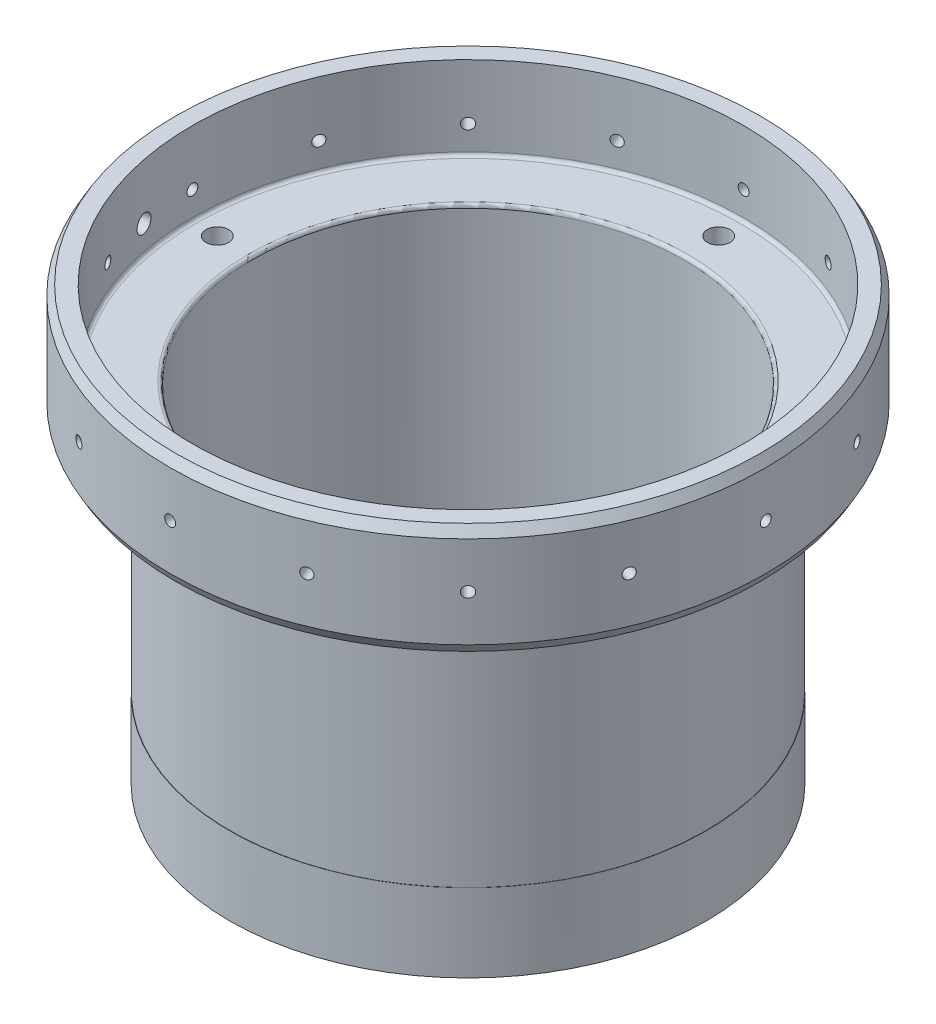
SolidWorks part; units mm, degrees
material "6061-T6 (SS)"
ref_plane "Front Plane" through (0, 0, 0) normal (0, 0, 1) x (1, 0, 0)
ref_plane "Top Plane" through (0, 0, 0) normal (0, 1, 0) x (1, 0, 0)
ref_plane "Right Plane" through (0, 0, 0) normal (1, 0, 0) x (0, 0, -1)
sketch "Sketch1" plane through (0, 0, 0) normal (0, 0, 1) x (1, 0, 0)
  line L0 (0, 0) -> (0, 9.1321) construction
  line L1 (0, 0) -> (-63.119, 0) construction
  line L2 (-63.119, 0) -> (-68.199, 0)
  line L3 (-68.199, 0) -> (-68.199, -25.4)
  line L4 (-68.199, -25.4) -> (-54.6024, -25.4)
  line L5 (-54.6024, -25.4) -> (-54.6024, -33.909)
  line L6 (-54.5516, -99.6696) -> (-49.4665, -99.6696)
  line L7 (-49.4665, -99.6696) -> (-49.4665, -19.05)
  line L8 (-49.4665, -19.05) -> (-63.119, -19.05)
  line L9 (-63.119, -19.05) -> (-63.119, 0)
  line L10 (-54.6024, -33.909) -> (-54.4881, -33.909)
  line L11 (-54.4881, -33.909) -> (-54.4881, -81.026)
  line L12 (-54.4881, -81.026) -> (-54.5516, -81.026)
  line L13 (-54.5516, -81.026) -> (-54.5516, -99.6696)
  dimension "D1" = 5.08
  dimension "D2" = 68.199
  dimension "D3" = 25.4
  dimension "D4" = 6.35
  dimension "D5" = 74.2696
  dimension "D6" = 49.4665
  dimension "D7" = 54.5516
  dimension "D8" = 8.509
  dimension "D9" = 47.117
  dimension "D10" = 54.6024
  dimension "D11" = 54.4881
revolve "Revolve6" add sketch "Sketch1" angle 360 about L0
sketch "Sketch2" plane through (0, 0, 0) normal (0, 1, 0) x (1, 0, 0)
  line L0 (0, 0) -> (-68.199, 0) construction
  line L1 (0, 0) -> (-66.8886, -13.305) construction
  circle A0 centre (0, 0) radius 68.199 construction
  dimension "D1" = 11.25
ref_plane "Plane1" through (-68.199, 0, 0) normal (-1, 0, 0) x (0, 0, 1)
sketch "Sketch3" plane through (-68.199, 0, 0) normal (-1, 0, 0) x (0, 0, 1)
  line L0 (0, 0) -> (0, -12.7) construction
  dimension "D1" = 12.7
hole_wizard "Tap Drill for M3x0.5 Tap1" positions "Sketch5" profile "Sketch4" hole size "M3x0.5" standard "Ansi Metric"
sketch "Sketch5" plane through (-68.199, 0, 0) normal (-1, 0, 0) x (0, 0, 1)
  point P1 (0, -12.7)
sketch "Sketch4" plane through (-68.199, -12.7, 0) normal (0, 1, 0) x (0, 0, 1)
  line L0 (0, 0) -> (0, 10.9111)
  line L1 (0, 10.9111) -> (1.25, 10.16)
  line L2 (1.25, 10.16) -> (1.25, 0)
  line L5 (1.25, 0) -> (0, 0)
  line L10 (0, 10.9111) -> (-1.25, 10.16) construction
  line L11 (0, -6.35) -> (0, 107.95) construction
  dimension "Hole Dia." = 2.5
  dimension "Hole Depth" = 10.16
  dimension "Drill Angle" = 118
pattern_circular "CirPattern1" count 16 over 360 about axis through (0, 0, 0) along (0, -1, 0) of "Tap Drill for M3x0.5 Tap1"
ref_plane "Plane2" through (-66.8886, 0, 13.305) normal (-0.9808, 0, 0.1951) x (0.1951, 0, 0.9808)
sketch "Sketch6" plane through (-66.8886, 0, 13.305) normal (-0.9808, 0, 0.1951) x (0.1951, 0, 0.9808)
  line L0 (0, 0) -> (0, -12.7) construction
  dimension "D1" = 12.7
hole_wizard "Tap Drill for #10-32 Tap1" positions "Sketch8" profile "Sketch7" hole size "#10-32" standard "Ansi Inch"
sketch "Sketch8" plane through (-66.8886, 0, 13.305) normal (-0.9808, 0, 0.1951) x (0.1951, 0, 0.9808)
  point P1 (0, -12.7)
sketch "Sketch7" plane through (-66.8886, -12.7, 13.305) normal (0, 1, 0) x (0.1951, 0, 0.9808)
  line L0 (0, 0) -> (0, 11.3733)
  line L1 (0, 11.3733) -> (2.0193, 10.16)
  line L2 (2.0193, 10.16) -> (2.0193, 0)
  line L5 (2.0193, 0) -> (0, 0)
  line L10 (0, 11.3733) -> (-2.0193, 10.16) construction
  line L11 (0, -6.35) -> (0, 107.95) construction
  dimension "Hole Dia." = 4.0386
  dimension "Hole Depth" = 10.16
  dimension "Drill Angle" = 118
sketch "Sketch9" plane through (0, -99.6696, 0) normal (0, -1, 0) x (1, 0, 0)
  line L0 (54.5516, 0) -> (49.4665, 0) construction
  circle A2 centre (0, 0) radius 49.4665 construction
  circle A3 centre (0, 0) radius 54.5516 construction
  point P9 (52.009, 0)
  dimension "D1" = 52.009
hole_wizard "Tap Drill for #4-40 Tap1" positions "3DSketch1" profile "Sketch10" hole size "#4-40" standard "Ansi Inch"
sketch3d "3DSketch1"
  point P0 (52.009, -99.6696, 0)
sketch "Sketch10" plane through (52.009, -99.6696, 0) normal (1, 0, 0) x (0, 0, -1)
  line L0 (0, 0) -> (0, 18.4592)
  line L1 (0, 18.4592) -> (1.1303, 17.78)
  line L2 (1.1303, 17.78) -> (1.1303, 0)
  line L5 (1.1303, 0) -> (0, 0)
  line L10 (0, 18.4592) -> (-1.1303, 17.78) construction
  line L11 (0, -6.35) -> (0, 107.95) construction
  dimension "Hole Dia." = 2.2606
  dimension "Hole Depth" = 17.78
  dimension "Drill Angle" = 118
pattern_circular "CirPattern2" count 16 over 360 of "Tap Drill for #4-40 Tap1"
sketch "Sketch12" plane through (0, -25.4, 0) normal (0, -1, 0) x (1, 0, 0)
  line L0 (0, 54.6024) -> (0, 57.3964) construction
  circle A0 centre (0, 0) radius 54.6024 construction
  circle A1 centre (0, 0) radius 54.6024 construction
  dimension "D1" = 2.794
hole_wizard "13/64 (0.20313) Diameter Hole1" positions "3DSketch2" profile "Sketch14" hole size "13/64" standard "Ansi Inch" end condition through all
sketch3d "3DSketch2"
  point P0 (0, -25.4, 57.3964)
sketch "Sketch14" plane through (0, -25.4, 57.3964) normal (1, 0, 0) x (0, 0, -1)
  line L0 (0, 0) -> (0, 25.4)
  line L1 (0, 25.4) -> (2.5798, 25.4)
  line L2 (2.5798, 25.4) -> (2.5798, 0)
  line L5 (2.5798, 0) -> (0, 0)
  line L11 (0, -6.35) -> (0, 107.95) construction
  dimension "Thru Hole Dia." = 5.1595
  dimension "Thru Hole Depth" = 25.4
pattern_circular "CirPattern3" count 4 over 360 about axis through (0, 0, 0) along (0, -1, 0) of "13/64 (0.20313) Diameter Hole1"
chamfer "Chamfer2" distance 1.27 angle 60 2 edges at (0, -25.4, -68.199) (0, 0, -68.199) first distance on face at (57.3964, -25.4, -2.5798) first distance on face at (0, 0, -68.199)
chamfer "Chamfer4" distance 0.762 angle 60 1 edges at (0, -99.6696, -54.5516) first distance on face at (0, -99.6696, -54.5516)
chamfer "Chamfer5" distance 0.762 angle 60 1 edges at (0, -99.6696, -49.4665) first distance on face at (0, -99.6696, 53.2318)
fillet "Fillet1" radius 0.762 2 edges at (0, -19.05, -63.119) (0, -19.05, -49.4665)
